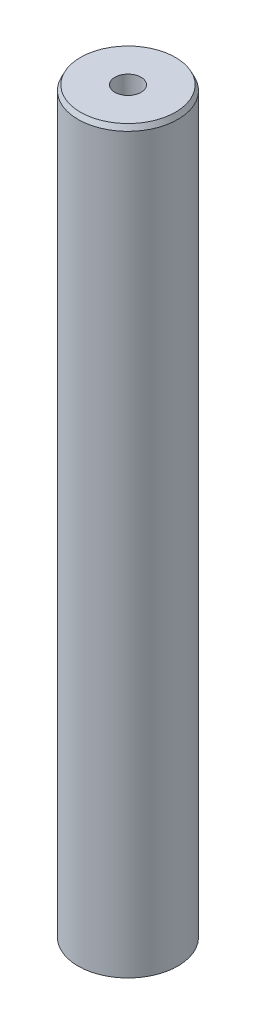
SolidWorks part; units mm, degrees
ref_plane "Front Plane" through (0, 0, 0) normal (0, 0, 1) x (1, 0, 0)
ref_plane "Top Plane" through (0, 0, 0) normal (0, 1, 0) x (1, 0, 0)
ref_plane "Right Plane" through (0, 0, 0) normal (1, 0, 0) x (0, 0, -1)
sketch "Sketch1" plane through (0, 0, 0) normal (0, 1, 0) x (1, 0, 0)
  circle A0 centre (0, 0) radius 12.5
  dimension "SHAFT_OD" = 25
extrude "Boss-Extrude1" add sketch "Sketch1" along normal blind 185.4905
sketch "Sketch2" plane through (0, 0, 0) normal (0, 1, 0) x (1, 0, 0)
  circle A0 centre (0, 0) radius 3.2823
  dimension "BORE_D" = 6.5645
extrude "Cut-Extrude1" cut sketch "Sketch2" along normal through all
chamfer "Chamfer1" distance 1.261 angle 25.548 2 edges at (0, 185.4905, 12.5) (0, 0, 12.5) first distance on face at (0, 185.4905, 12.5) first distance on face at (0, 0, 3.2823)
